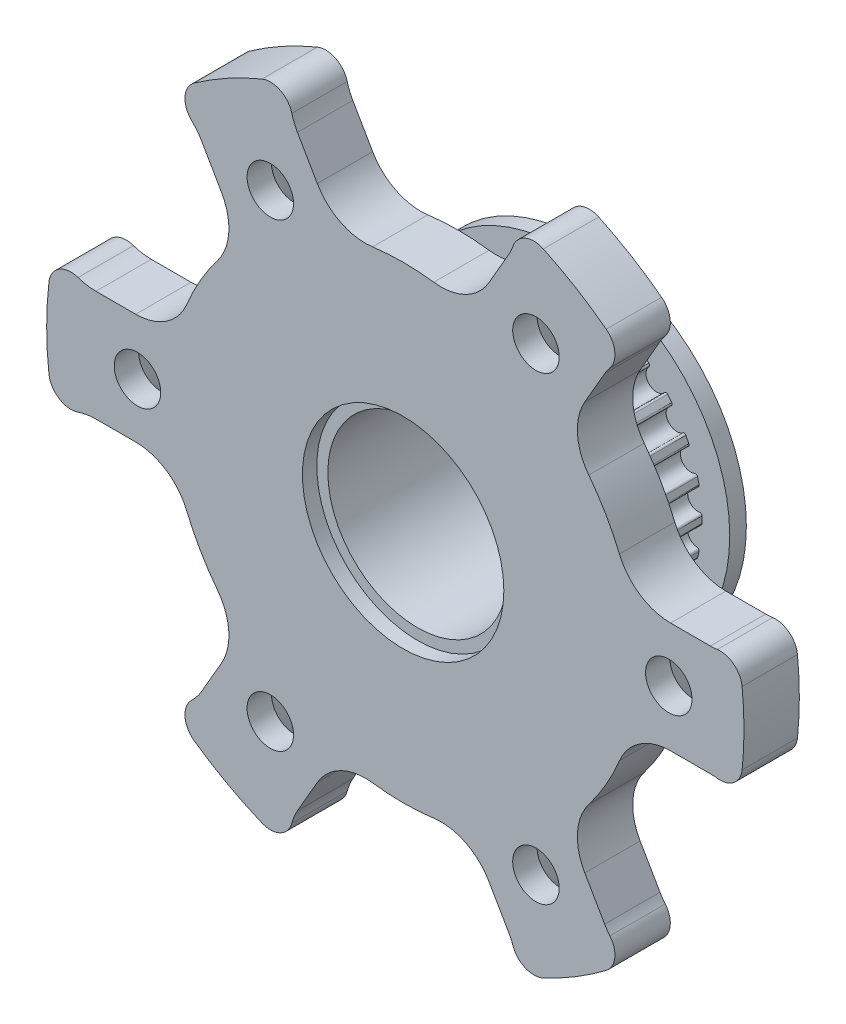
SolidWorks part; units mm, degrees
ref_plane "前视基准面" through (0, 0, 0) normal (0, 0, 1) x (1, 0, 0)
ref_plane "上视基准面" through (0, 0, 0) normal (0, 1, 0) x (1, 0, 0)
ref_plane "右视基准面" through (0, 0, 0) normal (1, 0, 0) x (0, 0, -1)
sketch "草图1" plane through (0, 0, 0) normal (0, 0, 1) x (-1, 0, 0)
  line L0 (-113.4201, 77.7903) -> (-117.011, 77.7903)
  line L1 (-124.7621, 64.3651) -> (-122.9666, 61.2552)
  line L2 (-122.9666, 104.3255) -> (-124.7621, 101.2156)
  line L3 (-117.011, 87.7903) -> (-113.4201, 87.7903)
  line L6 (-150.72, 109.3255) -> (-148.9245, 106.2156)
  line L7 (-133.4224, 106.2156) -> (-131.6269, 109.3255)
  line L10 (-168.9268, 87.7903) -> (-165.3359, 87.7903)
  line L11 (-157.5848, 101.2156) -> (-159.3803, 104.3255)
  line L14 (-159.3803, 61.2552) -> (-157.5848, 64.3651)
  line L15 (-165.3359, 77.7903) -> (-168.9268, 77.7903)
  line L18 (-131.6269, 56.2552) -> (-133.4224, 59.3651)
  line L19 (-148.9245, 59.3651) -> (-150.72, 56.2552)
  circle A1 centre (-141.1734, 82.7903) radius 44
  circle A3 centre (-117.1734, 82.7903) radius 2.1
  circle A5 centre (-129.1734, 103.5749) radius 2.1
  arc A7 (-108.7161, 71.0954) -> (-113.4201, 77.7903) centre (-113.4201, 72.7903) ccw
  arc A8 (-114.8167, 60.5289) -> (-108.7161, 71.0954) centre (-141.1734, 82.7903) ccw
  arc A9 (-122.9666, 61.2552) -> (-114.8167, 60.5289) centre (-118.6365, 63.7552) ccw
  arc A10 (-124.3978, 69.91) -> (-124.7621, 64.3651) centre (-120.432, 66.8651) ccw
  arc A11 (-124.3978, 69.91) -> (-121.631, 74.7024) centre (-141.1734, 82.7903) ccw
  arc A12 (-117.011, 77.7903) -> (-121.631, 74.7024) centre (-117.011, 72.7903) ccw
  arc A13 (-114.8167, 105.0517) -> (-122.9666, 104.3255) centre (-118.6365, 101.8255) ccw
  arc A20 (-108.7161, 94.4852) -> (-114.8167, 105.0517) centre (-141.1734, 82.7903) ccw
  arc A21 (-113.4201, 87.7903) -> (-108.7161, 94.4852) centre (-113.4201, 92.7903) ccw
  arc A22 (-121.631, 90.8783) -> (-117.011, 87.7903) centre (-117.011, 92.7903) ccw
  arc A23 (-121.631, 90.8783) -> (-124.3978, 95.6706) centre (-141.1734, 82.7903) ccw
  arc A24 (-124.7621, 101.2156) -> (-124.3978, 95.6706) centre (-120.432, 98.7156) ccw
  arc A25 (-147.274, 116.7467) -> (-150.72, 109.3255) centre (-146.3899, 111.8255) ccw
  arc A32 (-135.0729, 116.7467) -> (-147.274, 116.7467) centre (-141.1734, 82.7903) ccw
  arc A33 (-131.6269, 109.3255) -> (-135.0729, 116.7467) centre (-135.957, 111.8255) ccw
  arc A34 (-138.4066, 103.7586) -> (-133.4224, 106.2156) centre (-137.7525, 108.7156) ccw
  arc A35 (-138.4066, 103.7586) -> (-143.9403, 103.7586) centre (-141.1734, 82.7903) ccw
  arc A36 (-148.9245, 106.2156) -> (-143.9403, 103.7586) centre (-144.5944, 108.7156) ccw
  arc A37 (-173.6308, 94.4852) -> (-168.9268, 87.7903) centre (-168.9268, 92.7903) ccw
  arc A44 (-167.5302, 105.0517) -> (-173.6308, 94.4852) centre (-141.1734, 82.7903) ccw
  arc A45 (-159.3803, 104.3255) -> (-167.5302, 105.0517) centre (-163.7104, 101.8255) ccw
  arc A46 (-157.949, 95.6706) -> (-157.5848, 101.2156) centre (-161.9149, 98.7156) ccw
  arc A47 (-157.949, 95.6706) -> (-160.7159, 90.8783) centre (-141.1734, 82.7903) ccw
  arc A48 (-165.3359, 87.7903) -> (-160.7159, 90.8783) centre (-165.3359, 92.7903) ccw
  circle A49 centre (-153.1734, 103.5749) radius 2.1
  circle A56 centre (-165.1734, 82.7903) radius 2.1
  circle A57 centre (-153.1734, 62.0057) radius 2.1
  circle A58 centre (-129.1734, 62.0057) radius 2.1
  circle A59 centre (-141.1734, 82.7903) radius 9.1
  arc A60 (-167.5302, 60.5289) -> (-159.3803, 61.2552) centre (-163.7104, 63.7552) ccw
  arc A61 (-173.6308, 71.0954) -> (-167.5302, 60.5289) centre (-141.1734, 82.7903) ccw
  arc A68 (-168.9268, 77.7903) -> (-173.6308, 71.0954) centre (-168.9268, 72.7903) ccw
  arc A69 (-160.7159, 74.7024) -> (-165.3359, 77.7903) centre (-165.3359, 72.7903) ccw
  arc A70 (-160.7159, 74.7024) -> (-157.949, 69.91) centre (-141.1734, 82.7903) ccw
  arc A71 (-157.5848, 64.3651) -> (-157.949, 69.91) centre (-161.9149, 66.8651) ccw
  arc A72 (-135.0729, 48.834) -> (-131.6269, 56.2552) centre (-135.957, 53.7552) ccw
  arc A73 (-147.274, 48.834) -> (-135.0729, 48.834) centre (-141.1734, 82.7903) ccw
  arc A81 (-150.72, 56.2552) -> (-147.274, 48.834) centre (-146.3899, 53.7552) ccw
  arc A83 (-143.9403, 61.8221) -> (-148.9245, 59.3651) centre (-144.5944, 56.8651) ccw
  arc A85 (-143.9403, 61.8221) -> (-138.4066, 61.8221) centre (-141.1734, 82.7903) ccw
  arc A87 (-133.4224, 59.3651) -> (-138.4066, 61.8221) centre (-137.7525, 56.8651) ccw
extrude "凸台-拉伸1" add sketch "草图1" along normal blind 5 contours A1 A87 L18 A72 A73 A81 L19 A83 A85 A71 L14 A60 A61 A68 L15 A69 A70 A59 A58 A57 A56 A49 A48 L10 A37 A44 A45 L11 A46 A47 A36 L6 A25 A32 A33 L7 A34 A35 A24 L2 A13 region at (183.9289, -82.7903, 0)
sketch "草图2" plane through (0, 0, 0) normal (0, 0, 1) x (1, 0, 0)
  arc A28 (153.6796, -83.0847) -> (153.6796, -82.4959) centre (141.1734, -82.7903) ccw
  arc A29 (153.4104, -80.1927) -> (153.2746, -79.6197) centre (141.1734, -82.7903) ccw
  arc A30 (152.4815, -77.4407) -> (152.2172, -76.9145) centre (141.1734, -82.7903) ccw
  arc A31 (150.943, -74.9771) -> (150.5645, -74.526) centre (141.1734, -82.7903) ccw
  arc A32 (148.8778, -72.9347) -> (148.4054, -72.583) centre (141.1734, -82.7903) ccw
  arc A33 (146.3972, -71.4236) -> (145.8565, -71.1903) centre (141.1734, -82.7903) ccw
  arc A34 (143.6351, -70.5253) -> (143.0552, -70.423) centre (141.1734, -82.7903) ccw
  arc A35 (140.7402, -70.2882) -> (140.1524, -70.3224) centre (141.1734, -82.7903) ccw
  arc A36 (137.8687, -70.7251) -> (137.3046, -70.894) centre (141.1734, -82.7903) ccw
  arc A37 (135.1753, -71.8125) -> (134.6654, -72.1069) centre (141.1734, -82.7903) ccw
  arc A38 (132.8054, -73.4916) -> (132.377, -73.8957) centre (141.1734, -82.7903) ccw
  arc A39 (130.8865, -75.6721) -> (130.5629, -76.1641) centre (141.1734, -82.7903) ccw
  arc A40 (129.5222, -78.2363) -> (129.3208, -78.7896) centre (141.1734, -82.7903) ccw
  arc A41 (128.786, -81.046) -> (128.7177, -81.6309) centre (141.1734, -82.7903) ccw
  arc A42 (128.7177, -83.9498) -> (128.786, -84.5346) centre (141.1734, -82.7903) ccw
  arc A43 (129.3208, -86.791) -> (129.5222, -87.3443) centre (141.1734, -82.7903) ccw
  arc A44 (130.5629, -89.4166) -> (130.8865, -89.9086) centre (141.1734, -82.7903) ccw
  arc A45 (132.377, -91.6849) -> (132.8054, -92.089) centre (141.1734, -82.7903) ccw
  arc A46 (134.6654, -93.4738) -> (135.1753, -93.7682) centre (141.1734, -82.7903) ccw
  arc A47 (137.3046, -94.6866) -> (137.8687, -94.8555) centre (141.1734, -82.7903) ccw
  arc A48 (140.1524, -95.2582) -> (140.7402, -95.2924) centre (141.1734, -82.7903) ccw
  arc A49 (143.0552, -95.1576) -> (143.6351, -95.0554) centre (141.1734, -82.7903) ccw
  arc A50 (145.8565, -94.3903) -> (146.3972, -94.1571) centre (141.1734, -82.7903) ccw
  arc A51 (148.4054, -92.9976) -> (148.8778, -92.646) centre (141.1734, -82.7903) ccw
  arc A52 (150.5645, -91.0547) -> (150.943, -90.6036) centre (141.1734, -82.7903) ccw
  arc A53 (152.2172, -88.6662) -> (152.4815, -88.14) centre (141.1734, -82.7903) ccw
  arc A54 (153.2746, -85.9609) -> (153.4104, -85.388) centre (141.1734, -82.7903) ccw
  circle A55 centre (141.1734, -82.7903) radius 9.1 construction
  circle A56 centre (141.1734, -82.7903) radius 9.1
  spline S0 degree 3 number of poles 68 (153.4104, -85.388) -> (153.6796, -83.0847)
  spline S1 degree 3 number of poles 68 (153.6796, -82.4959) -> (153.4104, -80.1927)
  spline S2 degree 3 number of poles 68 (153.2746, -79.6197) -> (152.4815, -77.4407)
  spline S3 degree 3 number of poles 68 (152.2172, -76.9145) -> (150.943, -74.9771)
  spline S4 degree 3 number of poles 68 (150.5645, -74.526) -> (148.8778, -72.9347)
  spline S5 degree 3 number of poles 68 (148.4054, -72.583) -> (146.3972, -71.4236)
  spline S6 degree 3 number of poles 68 (145.8565, -71.1903) -> (143.6351, -70.5253)
  spline S7 degree 3 number of poles 68 (143.0552, -70.423) -> (140.7402, -70.2882)
  spline S8 degree 3 number of poles 68 (140.1524, -70.3224) -> (137.8687, -70.7251)
  spline S9 degree 3 number of poles 68 (137.3046, -70.894) -> (135.1753, -71.8125)
  spline S10 degree 3 number of poles 68 (134.6654, -72.1069) -> (132.8054, -73.4916)
  spline S11 degree 3 number of poles 68 (132.377, -73.8957) -> (130.8865, -75.6721)
  spline S12 degree 3 number of poles 68 (130.5629, -76.1641) -> (129.5222, -78.2363)
  spline S13 degree 3 number of poles 68 (129.3208, -78.7896) -> (128.786, -81.046)
  spline S14 degree 3 number of poles 68 (128.7177, -81.6309) -> (128.7177, -83.9498)
  spline S15 degree 3 number of poles 68 (128.786, -84.5346) -> (129.3208, -86.791)
  spline S16 degree 3 number of poles 68 (129.5222, -87.3443) -> (130.5629, -89.4166)
  spline S17 degree 3 number of poles 68 (130.8865, -89.9086) -> (132.377, -91.6849)
  spline S18 degree 3 number of poles 68 (132.8054, -92.089) -> (134.6654, -93.4738)
  spline S19 degree 3 number of poles 68 (135.1753, -93.7682) -> (137.3046, -94.6866)
  spline S20 degree 3 number of poles 68 (137.8687, -94.8555) -> (140.1524, -95.2582)
  spline S21 degree 3 number of poles 68 (140.7402, -95.2924) -> (143.0552, -95.1576)
  spline S22 degree 3 number of poles 68 (143.6351, -95.0554) -> (145.8565, -94.3903)
  spline S23 degree 3 number of poles 68 (146.3972, -94.1571) -> (148.4054, -92.9976)
  spline S24 degree 3 number of poles 68 (148.8778, -92.646) -> (150.5645, -91.0547)
  spline S25 degree 3 number of poles 68 (150.943, -90.6036) -> (152.2172, -88.6662)
  spline S26 degree 3 number of poles 68 (152.4815, -88.14) -> (153.2746, -85.9609)
  dimension "D1" = 0
extrude "凸台-拉伸2" add sketch "草图2" against normal blind 11
sketch "草图7" plane through (0, 0, 0) normal (0, 0, -1) x (-1, 0, 0)
  circle A0 centre (-140.4695, -82.7903) radius 31.5
  circle A1 centre (-140.4695, -82.7903) radius 51.2004
  dimension "D1" = 63
extrude "切除-拉伸2" cut sketch "草图7" against normal blind 19.3
fillet "圆角1" radius 2 12 edges at (151.3626, -53.2338, 2.5) (131.0638, -52.7274, 2.5) (119.9143, -58.9212, 2.5) (109.6851, -76.1145, 2.5) (109.6851, -89.4662, 2.5) (119.9143, -106.6594, 2.5) (131.0638, -112.8533, 2.5) (151.3626, -112.3469, 2.5) (161.4508, -106.2858, 2.5) (171.4523, -77.1056, 2.5) (161.4508, -59.2949, 2.5) (171.4523, -88.475, 2.5)
sketch "草图8" plane through (0, 0, -11) normal (0, 0, -1) x (-1, 0, 0)
  circle A0 centre (-141.1734, -82.7903) radius 8.1
  circle A1 centre (-141.1734, -82.7903) radius 9.1
  dimension "D1" = 16.2
extrude "凸台-拉伸6" add sketch "草图8" against normal up to surface (16 mm away) up to face at (119.2734, -82.7903, 5)
sketch "草图9" plane through (0, 0, -11) normal (0, 0, -1) x (-1, 0, 0)
  circle A0 centre (-141.1734, -82.7903) radius 9.15
  dimension "D1" = 18.3
extrude "切除-拉伸3" cut sketch "草图9" against normal blind 1.5
sketch "草图10" plane through (0, 0, 0) normal (0, 0, -1) x (-1, 0, 0)
  circle A0 centre (-141.1734, -82.7903) radius 14.0096
  arc A1 (-145.8565, -71.1903) -> (-146.3972, -71.4236) centre (-141.1734, -82.7903) ccw construction
  circle A2 centre (-141.1734, -82.7903) radius 9.15 construction
  circle A3 centre (-141.1734, -82.7903) radius 9.15
  dimension "D1" = 1.5
extrude "凸台-拉伸7" add sketch "草图10" along normal blind 1
sketch "草图11" plane through (0, 0, -11) normal (0, 0, -1) x (-1, 0, 0)
  circle A0 centre (-141.1734, -82.7903) radius 15.0096
  circle A1 centre (-141.1734, -82.7903) radius 9.15
extrude "凸台-拉伸8" add sketch "草图11" against normal blind 1.5
chamfer "倒角1" distance 3 angle 45 1 edges at (155.1831, -82.7903, 0)
chamfer "倒角2" distance 2.8 angle 45 6 edges at (167.2734, -82.7903, 0) (155.2734, -62.0057, 0) (131.2734, -62.0057, 0) (119.2734, -82.7903, 0) (131.2734, -103.5749, 0) (155.2734, -103.5749, 0)
sketch "草图12" plane through (0, 0, 5) normal (0, 0, 1) x (1, 0, 0)
  circle A0 centre (141.1734, -82.7903) radius 9.1
  dimension "D1" = 18.2
extrude "切除-拉伸4" cut sketch "草图12" against normal blind 1.3
